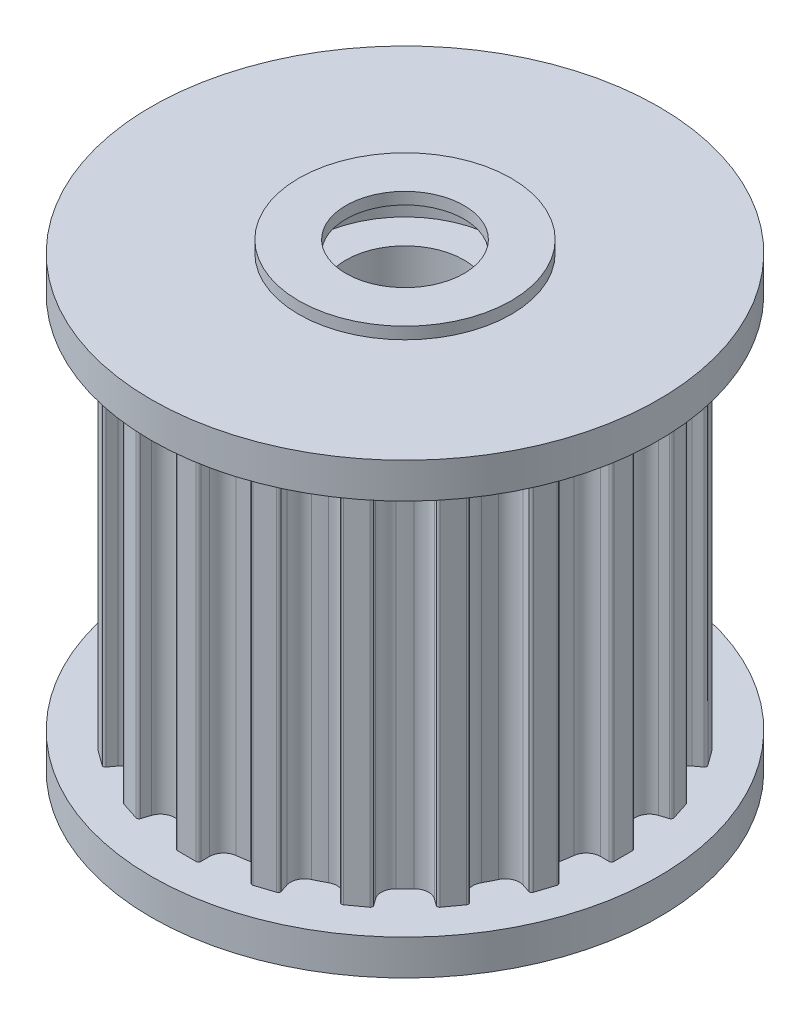
SolidWorks part; units mm, degrees
material "6061 Сплав"
ref_plane "Спереди" through (0, 0, 0) normal (0, 0, 1) x (1, 0, 0)
ref_plane "Сверху" through (0, 0, 0) normal (0, 1, 0) x (1, 0, 0)
ref_plane "Справа" through (0, 0, 0) normal (1, 0, 0) x (0, 0, -1)
sketch "Эскиз1" plane through (0, 0, 0) normal (0, 1, 0) x (1, 0, 0)
  circle A0 centre (0, 0) radius 8.25
  circle A1 centre (0, 0) radius 2.5
  dimension "D1" = 16.5
  dimension "D2" = 5
extrude "Бобышка-Вытянуть1" add sketch "Эскиз1" along normal blind 16
sketch "Эскиз2" plane through (0, 16, 0) normal (0, 1, 0) x (1, 0, 0)
  line L0 (0, 0) -> (0, 50000) construction
  line L1 (0, 0) -> (50000, 0) construction
  line L2 (0, 8.25) -> (50000, 8.25) construction
  line L4 (-0.5, 9.25) -> (0.5, 9.25)
  line L5 (-0.5, 9.25) -> (-0.5, 7.25)
  line L6 (-0.5, 7.25) -> (0.5, 7.25)
  line L7 (0.5, 9.25) -> (0.5, 7.25)
  line L8 (-0.5, 9.25) -> (0.5, 7.25) construction
  line L9 (-0.5, 7.25) -> (0.5, 9.25) construction
  point P8 (0, 8.25)
  dimension "D1" = 2
  dimension "D2" = 1
extrude "Бобышка-Вытянуть2" add sketch "Эскиз2" against normal up to surface (16 mm away) up to face at (0, 0, 8.25)
fillet "Скругление1" radius 0.6 2 edges at (-0.5, 8, -8.2348) (0.5, 8, -8.2348)
fillet "Скругление2" radius 0.1 2 edges at (0.5, 8, -9.25) (-0.5, 8, -9.25)
pattern_circular "Круговой массив2" count 20 over 360 about axis through (0, 16, 0) along (0, 1, 0) of "Скругление2", "Скругление1", "Бобышка-Вытянуть2"
sketch "Эскиз3" plane through (0, 0, 0) normal (0, -1, 0) x (1, 0, 0)
  circle A0 centre (0, 0) radius 10.75
  dimension "D1" = 21.5
extrude "Вытянуть-Тонкостенный1" add sketch "Эскиз3" along normal blind 1.5 thin thin type one direction reverse wall 8.25
sketch "Эскиз4" plane through (0, 16, 0) normal (0, 1, 0) x (1, 0, 0)
  circle A0 centre (0, 0) radius 10.75
  dimension "D1" = 21.5
extrude "Вытянуть-Тонкостенный2" add sketch "Эскиз4" along normal blind 1.5 thin thin type one direction reverse wall 6.75
sketch "Эскиз5" plane through (0, -1.5, 0) normal (0, -1, 0) x (1, 0, 0)
  circle A0 centre (0, 0) radius 2.5
extrude "Вытянуть-Тонкостенный3" add sketch "Эскиз5" along normal blind 0.5 thin thin type one direction wall 2
sketch "Эскиз6" plane through (0, 17.5, 0) normal (0, 1, 0) x (1, 0, 0)
  circle A0 centre (0, 0) radius 2.5
extrude "Вытянуть-Тонкостенный4" add sketch "Эскиз6" along normal blind 0.5 thin thin type one direction wall 2
ref_axis "Ось1" through (0, 50, 0) along (0, -1, 0)
ref_plane "Плоскость1" through (0, 0, 0) normal (0.9511, 0, 0.309) x (0, -1, 0)
ref_plane "Плоскость2" through (0, 0, 0) normal (-0.309, 0, 0.9511) x (0, -1, 0)
sketch "Эскиз9" plane through (0, 0, 0) normal (0.9511, 0, 0.309) x (0, -1, 0)
  line L0 (0, -1.2899) -> (50000, -1.2899) construction
  line L1 (0, -1.0254) -> (0, -1.5544) construction
  line L2 (-8, -9.15) -> (-8, -50009.15) construction
  line L3 (-16, -9.15) -> (0, -9.15) construction
  circle A0 centre (-8, -1.2899) radius 1.5
  point P4 (0, -1.2899)
  point P9 (-8, -9.15)
  dimension "D1" = 3
extrude "Вырез-Вытянуть2" cut sketch "Эскиз9" against normal through all
sketch "Эскиз11" plane through (0, 0, 0) normal (0.9511, 0, 0.309) x (0, -1, 0)
  circle A0 centre (-8, -1.2899) radius 1.5
extrude "Бобышка-Вытянуть4" add sketch "Эскиз11" against normal blind 4 from offset 4 separate body offset against normal yes
sketch "Эскиз12" plane through (-7.6085, 0, -2.4721) normal (-0.9511, 0, -0.309) x (-0.309, 0, 0.9511)
  line L1 (0.1352, 8) -> (0.7126, 7)
  line L2 (0.7126, 7) -> (1.8673, 7)
  line L3 (1.8673, 7) -> (2.4446, 8)
  line L4 (2.4446, 8) -> (1.8673, 9)
  line L5 (1.8673, 9) -> (0.7126, 9)
  line L6 (0.7126, 9) -> (0.1352, 8)
  circle A0 centre (1.2899, 8) radius 1 construction
  dimension "D1" = 2
extrude "Вырез-Вытянуть3" cut sketch "Эскиз12" against normal blind 2
pattern_circular "Круговой массив3" count 2 every 90 about axis through (0, -2, 0) along (0, -1, 0) of "Вырез-Вытянуть2"
sketch "Эскиз13" plane through (0, 0, 0) normal (-0.309, 0, 0.9511) x (0, -1, 0)
  circle A0 centre (-8, -1.2899) radius 1.5
extrude "Бобышка-Вытянуть5" add sketch "Эскиз13" against normal blind 4 from offset 4 offset against normal yes
sketch "Эскиз14" plane through (2.4721, 0, -7.6085) normal (0.309, 0, -0.9511) x (-0.9511, 0, -0.309)
  line L1 (1.2899, 6.8453) -> (2.2899, 7.4226)
  line L2 (2.2899, 7.4226) -> (2.2899, 8.5774)
  line L3 (2.2899, 8.5774) -> (1.2899, 9.1547)
  line L4 (1.2899, 9.1547) -> (0.2899, 8.5774)
  line L5 (0.2899, 8.5774) -> (0.2899, 7.4226)
  line L6 (0.2899, 7.4226) -> (1.2899, 6.8453)
  circle A0 centre (1.2899, 8) radius 1 construction
  point P1 (2.2899, 8)
  dimension "D1" = 2
extrude "Вырез-Вытянуть4" cut sketch "Эскиз14" against normal blind 2
